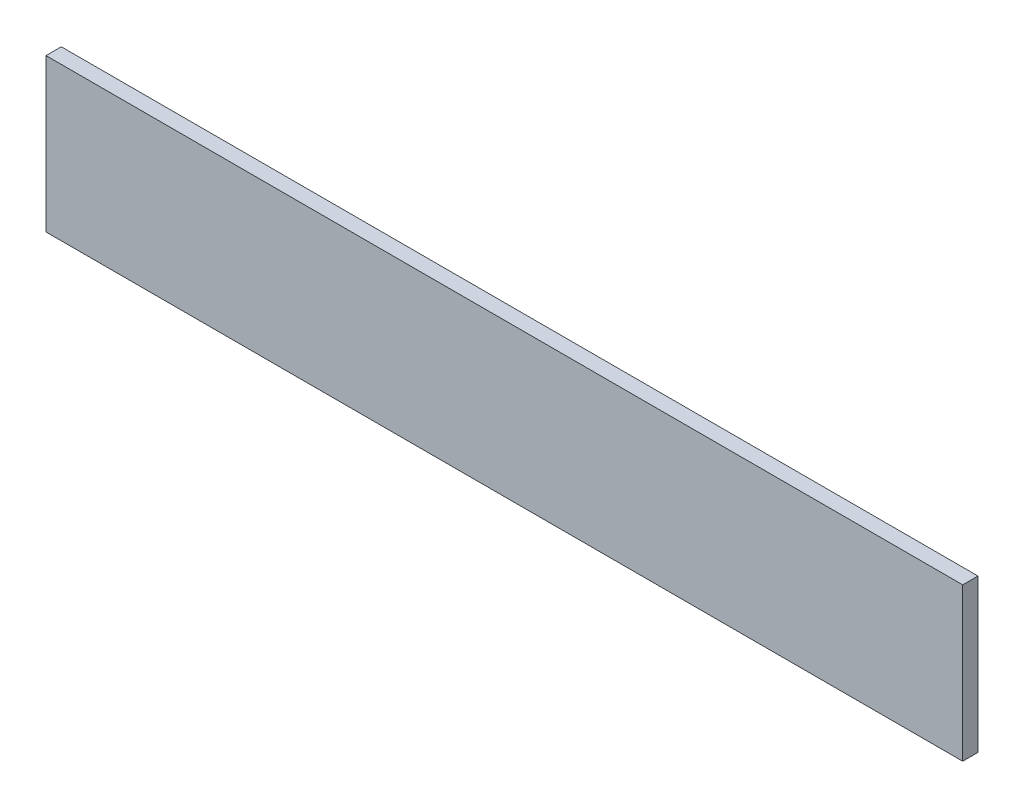
SolidWorks part; units mm, degrees
ref_plane "Спереди" through (0, 0, 0) normal (0, 0, 1) x (1, 0, 0)
ref_plane "Сверху" through (0, 0, 0) normal (0, 1, 0) x (1, 0, 0)
ref_plane "Справа" through (0, 0, 0) normal (1, 0, 0) x (0, 0, -1)
sketch "Эскиз1" plane through (0, 0, 0) normal (0, 0, 1) x (1, 0, 0)
  line L1 (0, 0) -> (120, 0)
  line L2 (0, 0) -> (0, -20)
  line L3 (0, -20) -> (120, -20)
  line L4 (120, 0) -> (120, -20)
extrude "Бобышка-Вытянуть1" add sketch "Эскиз1" along normal blind 2
sketch "Сгиб-Линии1" [suppressed] plane through (0, 0, 0) normal (0, 1, 0) x (1, 0, 0)
sketch "Граничная рамка1" [suppressed] plane through (0, 0, 0) normal (0, 1, 0) x (1, 0, 0)
